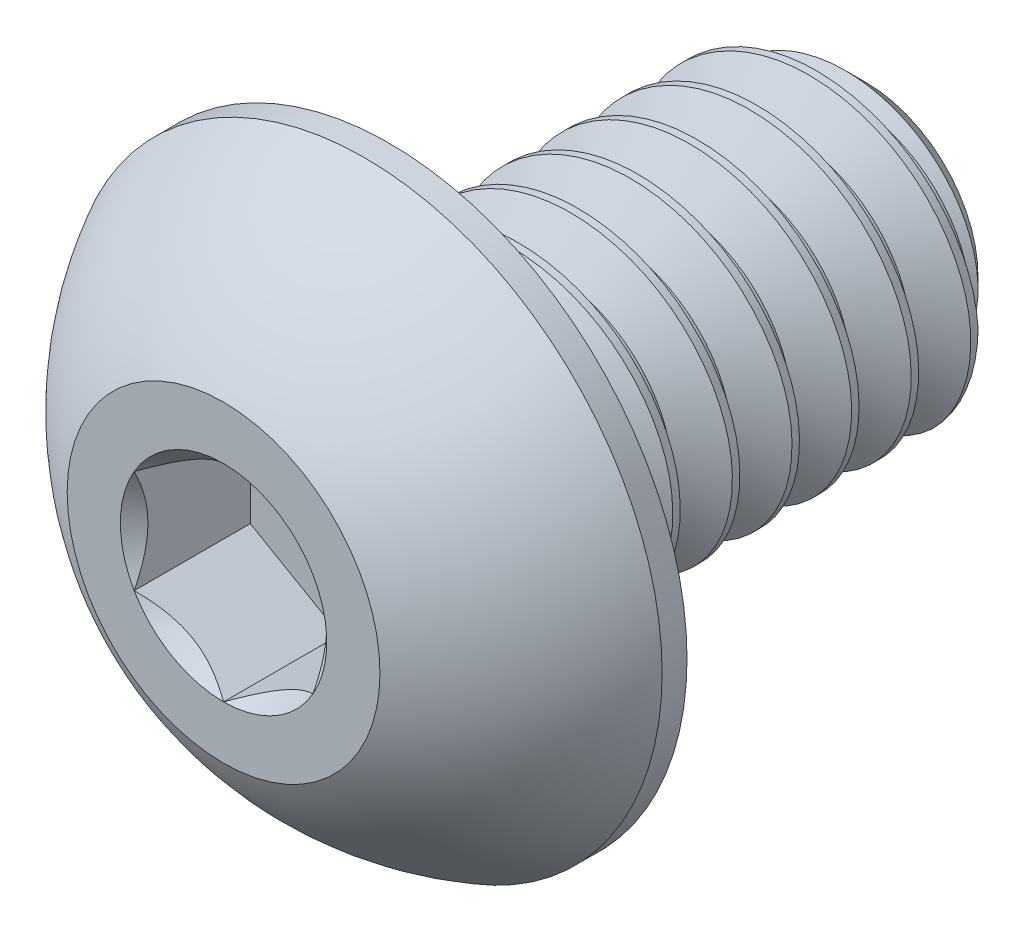
SolidWorks part; units mm, degrees
ref_plane "Front" through (0, 0, 0) normal (0, 0, 1) x (1, 0, 0)
ref_plane "Top" through (0, 0, 0) normal (0, 1, 0) x (1, 0, 0)
ref_plane "Right" through (0, 0, 0) normal (1, 0, 0) x (0, 0, -1)
sketch "Sketch1" plane through (0, 0, 0) normal (1, 0, 0) x (0, 0, -1)
  line L2 (2.2098, 2.0828) -> (8.5598, 2.0828)
  line L3 (8.5598, 2.0828) -> (8.5598, 0)
  line L4 (8.5598, 0) -> (2.2098, 0)
  line L6 (1.8783, 3.9624) -> (2.2098, 3.9624) construction
  line L7 (8.5598, 2.0828) -> (8.5598, -2.0828) construction
  line L8 (0, 0) -> (2.2098, 0) construction
  line L9 (2.2098, 3.9624) -> (2.2098, -3.9624) construction
  line L11 (2.2098, 2.0828) -> (2.2098, 0)
  line L13 (0, 1.1906) -> (0, -1.1906) construction
  line L14 (0, 1.1906) -> (0, 2.0828) construction
  arc A3 (0, 2.0828) -> (1.8783, 3.9624) centre (3.9638, 0) cw construction
  dimension "D1" = 0.3315
revolve "Revolve1" add sketch "Sketch1" angle 360 mid plane about L4
sketch "Sketch3" plane through (0, 0, -8.5598) normal (0, 0, -1) x (-1, 0, 0)
  circle A0 centre (0, 0) radius 2.0828
curve "Helix/Spiral1" pitch 0.7937 height 7.1437 radius 2.0828 centre (0, 0, -8.5598) axis (0, 0, 1) start towards (0, 1, 0)
sketch "Sketch2" plane through (0, 0, 0) normal (1, 0, 0) x (0, 0, -1)
  line L0 (8.5598, 2.0828) -> (9.2543, 2.0828)
  line L1 (9.2543, 2.0828) -> (8.9567, 1.5672)
  line L2 (8.9567, 1.5672) -> (8.8575, 1.5672)
  line L3 (8.8575, 1.5672) -> (8.5598, 2.0828)
  line L4 (8.7086, 1.825) -> (9.1055, 1.825) construction
  dimension "D1" = 60
  dimension "D2" = 0.0992
  dimension "D3" = 0.3969
chamfer "Chamfer1" distance 0.5953 angle 45 1 edges at (0, 2.0828, -8.5598)
sweep "Cut-Sweep1" cut profiles "Sketch2" path "Helix/Spiral1" align with end faces yes
sketch "Sketch7" plane through (0, 0, 0) normal (1, 0, 0) x (0, 0, -1)
  line L6 (1.8783, 3.9624) -> (2.2098, 3.9624) construction
  line L8 (0, 0) -> (2.2098, 0) construction
  line L11 (2.2098, 3.9624) -> (2.2098, -3.9624) construction
  line L12 (1.8783, 3.9624) -> (2.2098, 3.9624)
  line L13 (0, 0) -> (2.2098, 0)
  line L14 (0, 1.1906) -> (0, -1.1906) construction
  line L15 (2.2098, 3.9624) -> (2.2098, 0)
  line L16 (0, 2.0828) -> (0, 0)
  arc A2 (1.8783, 3.9624) -> (0, 2.0828) centre (3.9638, 0) ccw construction
  arc A3 (1.8783, 3.9624) -> (0, 2.0828) centre (3.9638, 0) ccw
revolve "Revolve2" add sketch "Sketch7" angle 360 mid plane about L13
sketch "Sketch5" plane through (0, 0, 0) normal (0, 0, 1) x (1, 0, 0)
  line L1 (1.1906, -0.6874) -> (1.1906, 0.6874)
  line L2 (1.1906, 0.6874) -> (0, 1.3748)
  line L3 (0, 1.3748) -> (-1.1906, 0.6874)
  line L4 (-1.1906, 0.6874) -> (-1.1906, -0.6874)
  line L5 (-1.1906, -0.6874) -> (0, -1.3748)
  line L6 (0, -1.3748) -> (1.1906, -0.6874)
  circle A0 centre (0, 0) radius 1.1906 construction
extrude "Cut-Extrude2" cut sketch "Sketch5" against normal blind 1.5469
sketch "Sketch6" plane through (0, 0, 0) normal (0, 0, 1) x (1, 0, 0)
  circle A0 centre (0, 0) radius 1.3748
extrude "Cut-Extrude3" cut sketch "Sketch6" against normal blind 1.5469 draft 45
sketch "Sketch9" [suppressed] plane through (0, 0, -1.4986) normal (0, 0, 1) x (1, 0, 0)
  circle A2 centre (0, 0) radius 1.4224
extrude "Boss-Extrude2" [suppressed] add sketch "Sketch9" against normal offset from surface (12.7 mm away) 31.75 up to face at (0, 1.4875, -8.5598)
sketch "Sketch10" plane through (0, 0, 0) normal (1, 0, 0) x (0, 0, -1)
  line L0 (8.5598, 2.0828) -> (8.5598, -2.0828) construction
  point P0 (7.3692, -2.0828)
  dimension "D1" = 1.1906
equation "\"D3@Helix/Spiral1\" = \"Lg@Sketch1\" + \"D4@Helix/Spiral1\""
equation "\"D2@Sketch2\" = \"D4@Helix/Spiral1\" * .125"
equation "\"D3@Sketch2\" = \"D4@Helix/Spiral1\" * .5"
equation "\"D1@Chamfer1\" = \"D4@Helix/Spiral1\" * .75"
equation "\"D1@Cut-Extrude2\" = \"Head Ht@Sketch1\" * .7"
equation "\"D1@Sketch1\" = \"Head Ht@Sketch1\" * .15"
equation "\"D1@Sketch10\" = \"D4@Helix/Spiral1\" * 1.5"
equation "\"D1@Cut-Extrude3\" = \"D1@Cut-Extrude2\""
